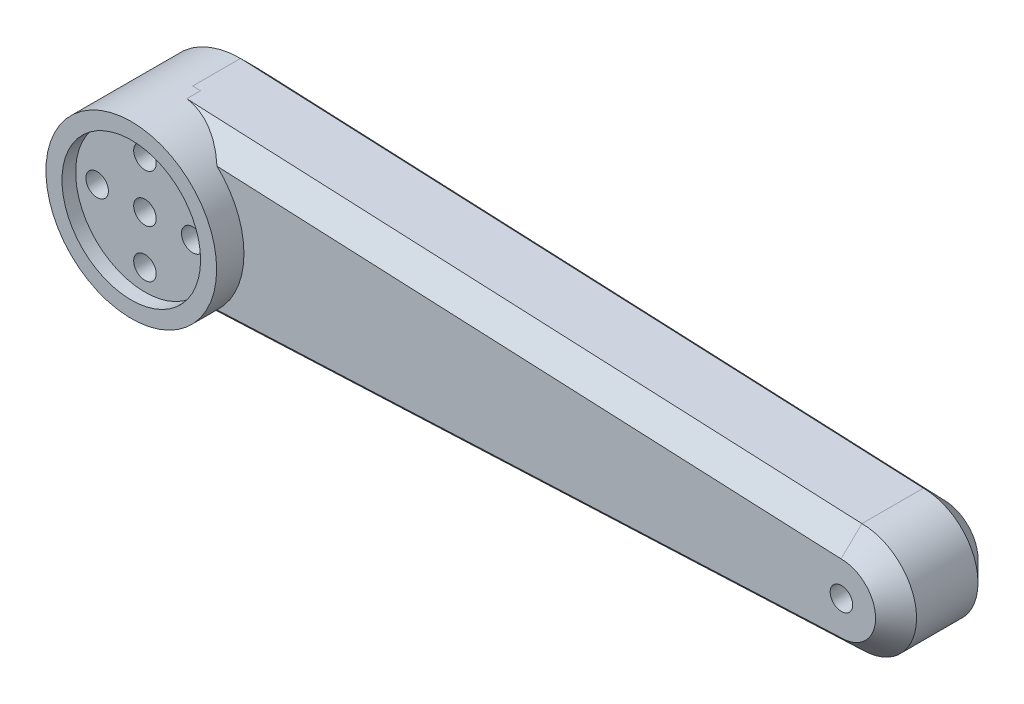
SolidWorks part; units mm, degrees
material "petg 20%"
ref_plane "Front Plane" through (0, 0, 0) normal (0, 0, 1) x (1, 0, 0)
ref_plane "Top Plane" through (0, 0, 0) normal (0, 1, 0) x (1, 0, 0)
ref_plane "Right Plane" through (0, 0, 0) normal (1, 0, 0) x (0, 0, -1)
sketch "Sketch1" plane through (0, 0, 0) normal (0, 0, 1) x (1, 0, 0)
  line L0 (0, 12.5) -> (100, 8)
  line L1 (0, -12.5) -> (100, -8)
  arc A0 (0, 12.5) -> (0, -12.5) centre (0, 0) ccw
  arc A1 (100, -8) -> (100, 8) centre (100, 0) ccw
  dimension "D1" = 25
  dimension "D2" = 16
  dimension "D3" = 100
extrude "Boss-Extrude1" add sketch "Sketch1" along normal blind 17
sketch "Sketch2" plane through (0, 0, 17) normal (0, 0, 1) x (1, 0, 0)
  circle A0 centre (0, 0) radius 12.5
  circle A1 centre (0, 0) radius 10.2
  dimension "D1" = 20.4
sketch "Sketch3" plane through (0, 0, 17) normal (0, 0, 1) x (1, 0, 0)
  circle A0 centre (0, 0) radius 1.65
  circle A1 centre (-7, 0) radius 1.65
  circle A2 centre (0, 7) radius 1.65
  circle A3 centre (7, 0) radius 1.65
  circle A4 centre (0, -7) radius 1.65
  point P14 (0, 0)
  dimension "D1" = 3.3
  dimension "D2" = 3.3
  dimension "D3" = 7
  dimension "D4" = 4
extrude "Cut-Extrude2" cut sketch "Sketch3" against normal through all
sketch "Sketch4" plane through (0, 0, 17) normal (0, 0, 1) x (1, 0, 0)
  circle A0 centre (100, 0) radius 1.65
  dimension "D1" = 3.3
extrude "Cut-Extrude3" cut sketch "Sketch4" against normal through all
sketch "Sketch5" plane through (0, 0, 0) normal (0, 0, -1) x (-1, 0, 0)
  circle A0 centre (0, 0) radius 3
  circle A1 centre (-7, 0) radius 3
  circle A2 centre (0, 7) radius 3
  circle A3 centre (7, 0) radius 3
  circle A4 centre (0, -7) radius 3
  point P15 (0, 0)
  dimension "D1" = 6
  dimension "D2" = 6
  dimension "D3" = 4
extrude "Cut-Extrude4" cut sketch "Sketch5" against normal blind 2
chamfer "Chamfer5" distance 3 angle 45 4 edges at (108, 0, 0) (50, -10.25, 0) (-12.5, 0, 0) (50, 10.25, 0)
extrude "Boss-Extrude4" add sketch "Sketch2" against normal blind 7 contours A0 | A1
sketch "Sketch6" plane through (0, 0, 17) normal (0, 0, 1) x (1, 0, 0)
  circle A0 centre (0, 7) radius 1.55
  circle A1 centre (7, 0) radius 1.55
  circle A2 centre (0, 0) radius 1.55
  circle A3 centre (0, -7) radius 1.55
  circle A4 centre (-7, 0) radius 1.55
  circle A5 centre (0, 0) radius 12.5
  circle A6 centre (0, 0) radius 10.15
sketch "Sketch7" plane through (0, 0, 17) normal (0, 0, 1) x (1, 0, 0)
  line L0 (100, 8) -> (0.8739, 12.4694)
  line L1 (0.8739, -12.4694) -> (100, -8)
  arc A0 (0.8739, -12.4694) -> (0.8739, 12.4694) centre (0, 0) ccw
  arc A1 (100, -8) -> (100, 8) centre (100, 0) ccw
extrude "Cut-Extrude5" cut sketch "Sketch7" against normal blind 2
chamfer "Chamfer6" distance 3 angle 45 3 edges at (50.5614, -10.2247, 15) (108, 0, 15) (50.5614, 10.2247, 15)
extrude "Boss-Extrude5" add sketch "Sketch6" along normal blind 2 contours A0 A5 A6 region at (-12.1464, 0, 17)
